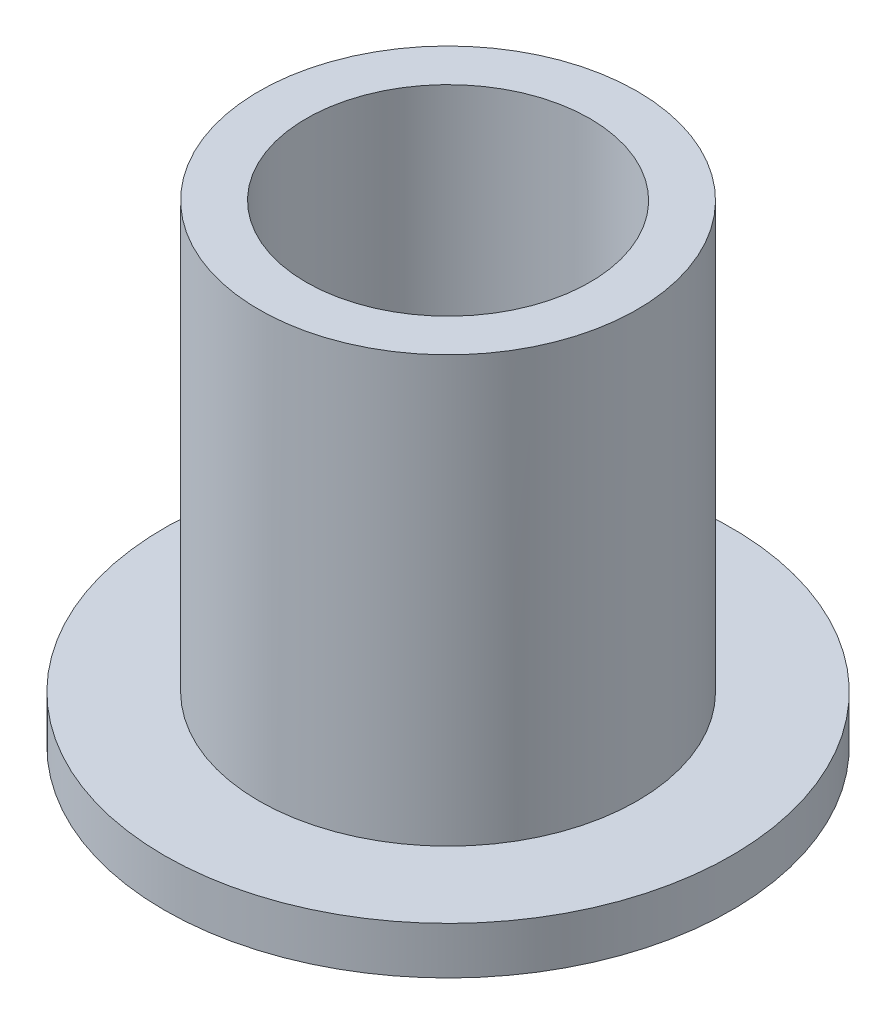
SolidWorks part; units mm, degrees
ref_plane "Front" through (0, 0, 0) normal (0, 0, 1) x (1, 0, 0)
ref_plane "Top" through (0, 0, 0) normal (0, 1, 0) x (1, 0, 0)
ref_plane "Right" through (0, 0, 0) normal (1, 0, 0) x (0, 0, -1)
sketch "Sketch1" plane through (0, 0, 0) normal (0, 1, 0) x (1, 0, 0)
  line L0 (0, 3) -> (0, 4) construction
  line L1 (3, 0) -> (-3, 0) construction
  line L2 (0, 6) -> (0, -6) construction
  line L3 (-4, 0) -> (4, 0) construction
  circle A0 centre (0, 0) radius 3
  circle A1 centre (0, 0) radius 4
  circle A2 centre (0, 0) radius 6
  point P10 (0, 0)
  point P11 (0, 0)
  point P12 (0, 0)
  point P18 (0, 3)
  point P19 (0, -3)
  dimension "ID" = 6
  dimension "OD" = 8
  dimension "FlangeOD" = 12
sketch "Sketch2" plane through (0, 0, 0) normal (1, 0, 0) x (0, 0, -1)
  line L0 (0, 0) -> (0, 10) construction
  line L1 (0, 10) -> (4, 10) construction
  line L2 (4, 10) -> (4, 0) construction
  line L3 (-6, 0) -> (-6, 1) construction
  line L4 (6, 0) -> (-6, 0) construction
  line L5 (3, 0) -> (3, 10) construction
  line L7 (-3, 0) -> (-3, 10) construction
  dimension "Length" = 10
  dimension "Flange" = 1
sketch "Sketch5" plane through (0, 0, 0) normal (1, 0, 0) x (0, 0, -1)
  line L0 (4, 10) -> (4, 0)
  line L1 (4, 0) -> (3, 0)
  line L2 (3, 0) -> (3, 10)
  line L3 (3, 10) -> (4, 10)
revolve "Revolve1" add sketch "Sketch5" angle 360 about L0
sketch "Sketch3" plane through (0, 0, 0) normal (0, 1, 0) x (1, 0, 0)
  circle A0 centre (0, 0) radius 6 construction
  circle A1 centre (0, 0) radius 4 construction
  circle A2 centre (0, 0) radius 6
  circle A3 centre (0, 0) radius 4
extrude "Boss-Extrude2" add sketch "Sketch3" along normal up to vertex (1 mm away) up to point (0, 1, 6)
ref_plane "Contact Plane 1" through (0, 10, 0) normal (0, 1, 0) x (1, 0, 0)
ref_plane "Contact Plane 2" through (0, 0, 0) normal (0, -1, 0) x (-1, 0, 0)
ref_axis "Center Axis 1" through (0, 0, 0) along (0, 1, 0)
